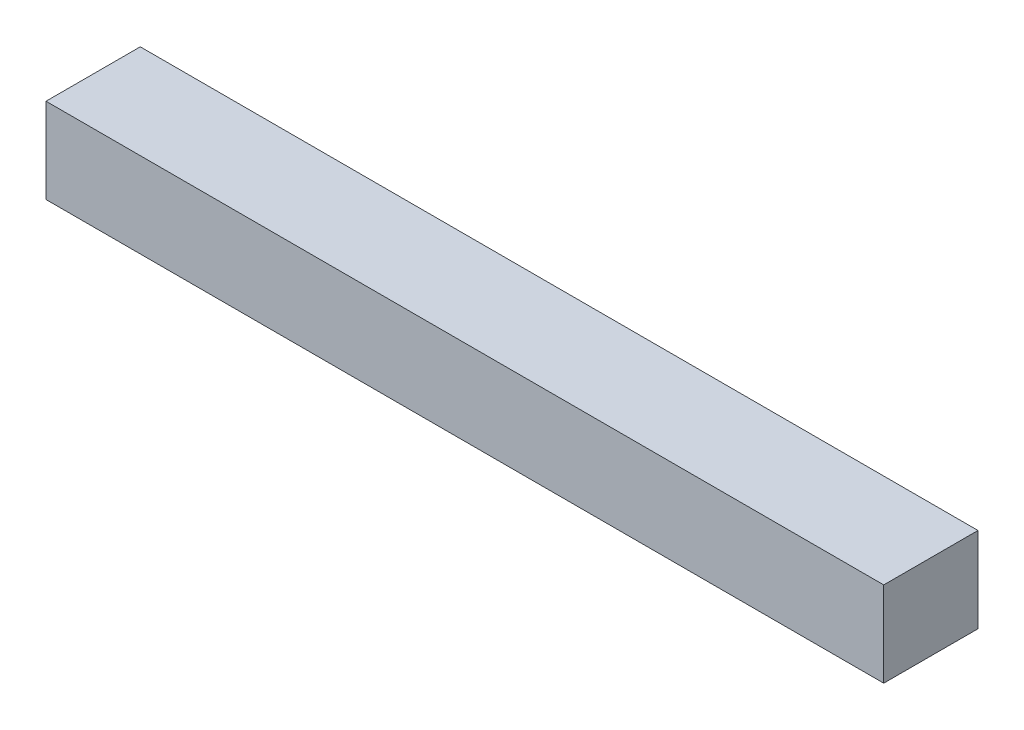
SolidWorks part; units mm, degrees
material "6061 합금"
ref_plane "정면" through (0, 0, 0) normal (0, 0, 1) x (1, 0, 0)
ref_plane "윗면" through (0, 0, 0) normal (0, 1, 0) x (1, 0, 0)
ref_plane "우측면" through (0, 0, 0) normal (1, 0, 0) x (0, 0, -1)
sketch "스케치1" plane through (0, 0, 0) normal (0, 1, 0) x (1, 0, 0)
  line L0 (-131.75, 9.5) -> (131.75, 9.5)
  line L1 (-137.75, 15.5) -> (137.75, 15.5)
  line L2 (-137.75, 15.5) -> (-137.75, -15.5)
  line L3 (-137.75, -15.5) -> (137.75, -15.5)
  line L4 (137.75, 15.5) -> (137.75, -15.5)
  line L5 (-137.75, 15.5) -> (137.75, -15.5) construction
  line L6 (-137.75, -15.5) -> (137.75, 15.5) construction
  line L7 (131.75, 9.5) -> (131.75, -9.5)
  line L8 (-131.75, -9.5) -> (131.75, -9.5)
  line L9 (-131.75, 9.5) -> (-131.75, -9.5)
  point P0 (0, 0)
  dimension "D1" = 31
  dimension "D2" = 275.5
  dimension "D3" = 6
extrude "보스-돌출1" add sketch "스케치1" along normal blind 28 contours L2 L1 L4 L3
extrude "컷-돌출1" cut sketch "스케치1<3>" along normal blind 16 from offset 6 contours L0 L9 L8 L7 region at (0, 0, 0)
sketch "스케치1<3>" plane through (0, 0, 0) normal (0, 1, 0) x (1, 0, 0) same geometry as "스케치1"
ref_plane "평면1" through (0, 14, 0) normal (0, 1, 0) x (1, 0, 0)
sketch "스케치2" plane through (0, 14, 0) normal (0, 1, 0) x (1, 0, 0)
  line L0 (-137.75, 0) -> (-174.25, 0) construction
  line L1 (-137.75, 15.5) -> (-137.75, -15.5) construction
  line L2 (137.75, 0) -> (175.75, 0) construction
  line L3 (137.75, 15.5) -> (137.75, -15.5) construction
  dimension "D1" = 36.5
  dimension "D2" = 38
